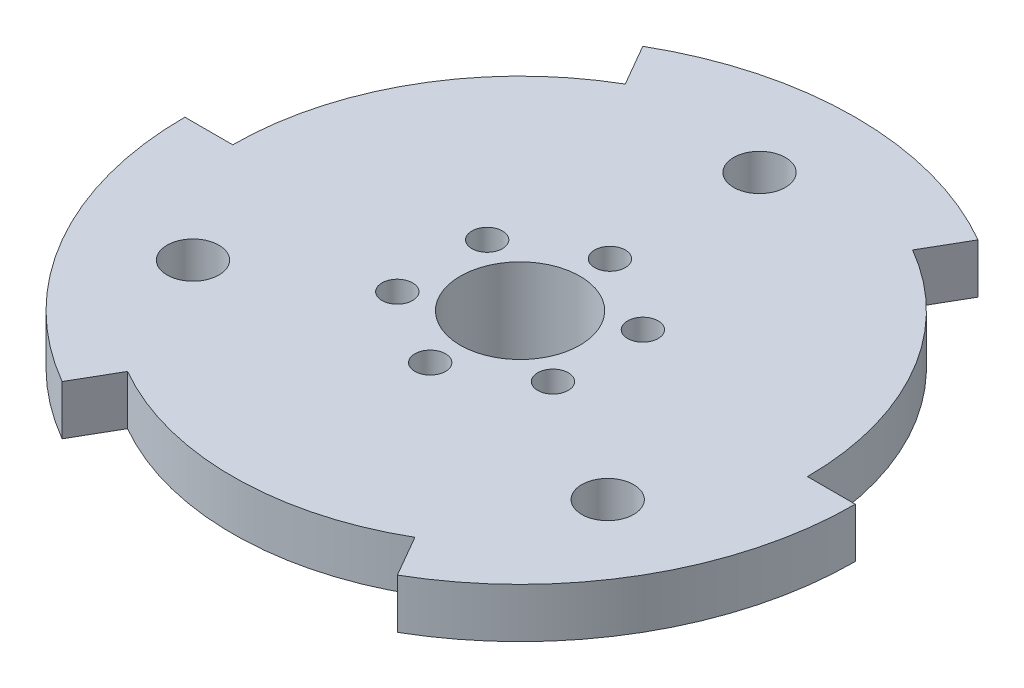
SolidWorks part; units mm, degrees
ref_plane "Front Plane" through (0, 0, 0) normal (0, 0, 1) x (1, 0, 0)
ref_plane "Top Plane" through (0, 0, 0) normal (0, 1, 0) x (1, 0, 0)
ref_plane "Right Plane" through (0, 0, 0) normal (1, 0, 0) x (0, 0, -1)
sketch "Sketch7" plane through (0, 0, 0) normal (0, 1, 0) x (1, 0, 0)
  line L1 (-11.3137, -11.3137) -> (11.3137, -11.3137)
  line L2 (-11.3137, -11.3137) -> (-11.3137, 11.3137)
  line L3 (-11.3137, 11.3137) -> (11.3137, 11.3137)
  line L4 (11.3137, -11.3137) -> (11.3137, 11.3137)
  line L5 (-11.3137, -11.3137) -> (11.3137, 11.3137) construction
  line L6 (-11.3137, 11.3137) -> (11.3137, -11.3137) construction
  circle A0 centre (0, 0) radius 16.1
  point P0 (0, 0)
  dimension "D1" = 32
extrude "Boss-Extrude2" add sketch "Sketch7" along normal blind 5 contours L1 L4 L3 L2 | A0 L4 L1 L2 L3 region at (0, 0, 0) region at (-15.6446, 0, 0)
sketch "Sketch1" plane through (0, 5, 0) normal (0, 1, 0) x (1, 0, 0)
  line L0 (0, 0) -> (0, 35.4208) construction
  line L1 (-20, -20) -> (20, -20)
  line L2 (-20, -20) -> (-20, 20)
  line L3 (-20, 20) -> (20, 20)
  line L4 (20, -20) -> (20, 20)
  line L5 (-20, -20) -> (20, 20) construction
  line L6 (-20, 20) -> (20, -20) construction
  line L7 (17.5, 30.3109) -> (15, 25.9808)
  line L8 (-17.5, 30.3109) -> (-15, 25.9808)
  line L9 (17.5, -30.3109) -> (15, -25.9808)
  line L10 (35, 0) -> (30, 0)
  line L11 (-35, 0) -> (-30, 0)
  line L12 (-17.5, -30.3109) -> (-15, -25.9808)
  circle A0 centre (0, 0) radius 6.25
  circle A1 centre (0, 25) radius 2.7073
  circle A2 centre (21.6506, -12.5) radius 2.7073
  circle A3 centre (-21.6506, -12.5) radius 2.7073
  circle A4 centre (0, 0) radius 30
  arc A5 (17.5, 30.3109) -> (-17.5, 30.3109) centre (0, 0) ccw
  arc A6 (17.5, -30.3109) -> (35, 0) centre (0, 0) ccw
  arc A7 (-35, 0) -> (-17.5, -30.3109) centre (0, 0) ccw
  point P0 (0, 0)
  point P18 (0, 0)
  point P21 (0, 35)
  point P34 (0, 0)
  dimension "D2" = 12.5
  dimension "D6" = 60
  dimension "D7" = 5
  dimension "D8" = 35
  dimension "D9" = 3
  dimension "D1" = 25
  dimension "D3" = 40
  dimension "D4" = 40
  dimension "D5" = 3
extrude "Boss-Extrude1" add sketch "Sketch1" along normal blind 5.18 contours L11 A7 L12 A4 | L9 A6 L10 A4 | L7 A5 L8 A4 | L2 A3 | L4 A2 | A1 | L2 A3 | L4 A2 | A0 | A4 region at (-21.9823, 5, 12.5) region at (-19.5694, 5, 12.5) region at (19.5694, 5, 12.5) region at (21.9823, 5, 12.5) region at (0, 5, -31.0964) region at (26.9303, 5, 15.5482) region at (-26.9303, 5, 15.5482) region at (0, 5, 0) region at (0, 5, -25)
sketch "Sketch5" [suppressed] plane through (0, 0, 0) normal (1, 0, 0) x (0, 0, -1)
  line L0 (-10.331, 15) -> (10.331, 0) construction
  line L1 (10, 5) -> (-10, 5)
  line L2 (10, 5) -> (10, 10)
  line L3 (10, 10) -> (-10, 10)
  line L4 (-10, 5) -> (-10, 10)
  line L5 (10, 5) -> (-10, 10) construction
  line L6 (10, 10) -> (-10, 5) construction
  line L7 (20, 7.5) -> (-20, 7.5) construction
  line L8 (20, 15) -> (20, 0) construction
  line L9 (-20, 15) -> (-20, 0) construction
  line L10 (-10.3541, 15) -> (-10.3078, 15) construction
  line L11 (-10.3541, 0) -> (20, 0) construction
  point P0 (0, 7.5)
  dimension "D1" = 20
  dimension "D2" = 5
sketch "Sketch3" [suppressed] plane through (0, 0, -20) normal (0, 0, -1) x (-1, 0, 0)
  line L3 (15.1539, 15) -> (15.1539, 3) construction
  line L4 (20, 15) -> (10.3078, 15) construction
  circle A0 centre (15.1539, 3) radius 1.6
  dimension "D2" = 3.2
  dimension "D1" = 12
sketch "Sketch2" [suppressed] plane through (0, 0, 20) normal (0, 0, 1) x (1, 0, 0)
  line L0 (0, 27.8717) -> (0, -11.9207) construction
  line L1 (20, 2) -> (10, 2)
  line L3 (10, 2) -> (10, 0)
  line L4 (-20, 0) -> (20, 0) construction
  line L5 (20, 15) -> (20, 0) construction
  circle A0 centre (10, 2) radius 1.6
  circle A1 centre (-10, 2) radius 1.6
  dimension "D3" = 3.2
  dimension "D1" = 10
  dimension "D2" = 2
sketch "Sketch6" plane through (0, 10.18, 0) normal (0, 1, 0) x (1, 0, 0)
  circle A9 centre (0, -9.385) radius 1.6
  circle A10 centre (-8.1276, -4.6925) radius 1.6
  circle A11 centre (-8.1276, 4.6925) radius 1.6
  circle A12 centre (0, 9.385) radius 1.6
  circle A13 centre (8.1276, 4.6925) radius 1.6
  circle A14 centre (8.1276, -4.6925) radius 1.6
  point P16 (0, 0)
  dimension "D2" = 9.385
  dimension "D1" = 3.2
  dimension "D3" = 9.385
extrude "Cut-Extrude1" cut sketch "Sketch6" along normal through all and the other way through all
fillet "Fillet2" [suppressed] radius 5
sketch "Sketch9" plane through (0, 10.18, 0) normal (0, 1, 0) x (1, 0, 0)
  line L6 (-30, 0) -> (-35, 0)
  line L7 (-17.5, -30.3109) -> (-15, -25.9808)
  line L8 (15, -25.9808) -> (17.5, -30.3109)
  line L9 (35, 0) -> (30, 0)
  line L10 (15, 25.9808) -> (17.5, 30.3109)
  line L11 (-17.5, 30.3109) -> (-15, 25.9808)
  line L12 (-30, 0) -> (-35, 0)
  line L13 (-17.5, -30.3109) -> (-15, -25.9808)
  line L14 (15, -25.9808) -> (17.5, -30.3109)
  line L15 (35, 0) -> (30, 0)
  line L16 (15, 25.9808) -> (17.5, 30.3109)
  line L17 (-17.5, 30.3109) -> (-15, 25.9808)
  arc A6 (-35, 0) -> (-17.5, -30.3109) centre (0, 0) ccw
  arc A7 (-15, -25.9808) -> (15, -25.9808) centre (0, 0) ccw
  arc A8 (17.5, -30.3109) -> (35, 0) centre (0, 0) ccw
  arc A9 (30, 0) -> (15, 25.9808) centre (0, 0) ccw
  arc A10 (17.5, 30.3109) -> (-17.5, 30.3109) centre (0, 0) ccw
  arc A11 (-15, 25.9808) -> (-30, 0) centre (0, 0) ccw
  arc A12 (-35, 0) -> (-17.5, -30.3109) centre (0, 0) ccw
  arc A13 (-15, -25.9808) -> (15, -25.9808) centre (0, 0) ccw
  arc A14 (17.5, -30.3109) -> (35, 0) centre (0, 0) ccw
  arc A15 (30, 0) -> (15, 25.9808) centre (0, 0) ccw
  arc A16 (17.5, 30.3109) -> (-17.5, 30.3109) centre (0, 0) ccw
  arc A17 (-15, 25.9808) -> (-30, 0) centre (0, 0) ccw
  circle M14 centre (8.1276, -4.6925) radius 1.6
  circle M15 centre (8.1276, 4.6925) radius 1.6
  circle M16 centre (0, 9.385) radius 1.6
  circle M17 centre (-8.1276, 4.6925) radius 1.6
  circle M18 centre (-8.1276, -4.6925) radius 1.6
  circle M31 centre (21.6506, -12.5) radius 2.7073
  circle M32 centre (0, 25) radius 2.7073
  circle M33 centre (-21.6506, -12.5) radius 2.7073
  circle M34 centre (0, 0) radius 6.25
  dimension "D1" = 0
extrude "Cut-Extrude2" cut sketch "Sketch9" against normal through all contours M33 | M34 | M31 | M32 | M14 | M15 | M16 | M17 | M18 region at (8.1276, 10.18, 4.6925) region at (8.1276, 10.18, -4.6925) region at (0, 10.18, -9.385) region at (-8.1276, 10.18, -4.6925) region at (-8.1276, 10.18, 4.6925) region at (21.6506, 10.18, 12.5) region at (0, 10.18, -25) region at (-21.6506, 10.18, 12.5) region at (0, 10.18, 0)
